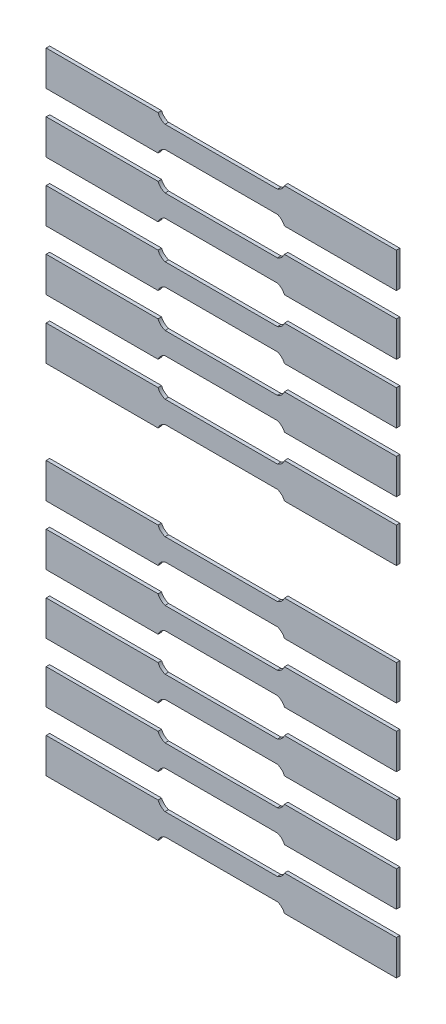
SolidWorks part; units mm, degrees
ref_plane "Ground Plane" through (0, 0, 0) normal (0, 0, 1) x (1, 0, 0)
ref_plane "Center Plane" through (0, 0, 0) normal (0, 1, 0) x (1, 0, 0)
ref_plane "Left Plane" through (0, 0, 0) normal (1, 0, 0) x (0, 0, -1)
ref_axis "FRONT (X)" through (88.99, 0, 0) along (-1, 0, 0)
ref_axis "LEFT (Y)" through (0, 55, 0) along (0, -1, 0)
ref_axis "UP (Z)" through (0, 0, 55) along (0, 0, -1)
sketch "Sketch1" plane through (0, 0, 0) normal (0, 0, 1) x (1, 0, 0)
  line L0 (0, 10) -> (0, 0)
  line L1 (66, 1.875) -> (66.044, 1.875)
  line L2 (66, 8.125) -> (66.044, 8.125)
  line L3 (34, 1.875) -> (33.956, 1.875)
  line L4 (0, 27) -> (0, 17)
  line L5 (66, 18.875) -> (66.044, 18.875)
  line L6 (66, 25.125) -> (66.044, 25.125)
  line L7 (34, 18.875) -> (33.956, 18.875)
  line L8 (0, 17) -> (31.956, 17)
  line L9 (0, 27) -> (31.956, 27)
  line L10 (100, 17) -> (100, 27)
  line L11 (49.956, 25.125) -> (66, 25.125)
  line L12 (66, 18.875) -> (50, 18.875)
  line L13 (50, 18.875) -> (34, 18.875)
  line L14 (33.956, 25.125) -> (49.956, 25.125)
  line L15 (68.044, 27) -> (100, 27)
  line L16 (68.044, 17) -> (100, 17)
  line L17 (0, 0) -> (31.956, 0)
  line L18 (0, 10) -> (31.956, 10)
  line L19 (100, 0) -> (100, 10)
  line L20 (49.956, 8.125) -> (66, 8.125)
  line L21 (66, 1.875) -> (50, 1.875)
  line L22 (50, 1.875) -> (34, 1.875)
  line L23 (33.956, 8.125) -> (49.956, 8.125)
  line L24 (68.044, 10) -> (100, 10)
  line L25 (68.044, 0) -> (100, 0)
  line L26 (33.956, 1.875) -> (31.956, 1.875) construction
  line L27 (31.956, 1.875) -> (31.956, 0) construction
  line L28 (33.956, 8.125) -> (31.956, 8.125) construction
  line L29 (31.956, 8.125) -> (31.956, 10) construction
  line L30 (68.044, 0) -> (68.044, 1.875) construction
  line L31 (68.044, 1.875) -> (66.044, 1.875) construction
  line L32 (66.044, 8.125) -> (68.044, 8.125) construction
  line L33 (68.044, 8.125) -> (68.044, 10) construction
  line L34 (33.956, 18.875) -> (31.956, 18.875) construction
  line L35 (31.956, 18.875) -> (31.956, 17) construction
  line L36 (33.956, 25.125) -> (31.956, 25.125) construction
  line L37 (31.956, 25.125) -> (31.956, 27) construction
  line L38 (68.044, 17) -> (68.044, 18.875) construction
  line L39 (68.044, 18.875) -> (66.044, 18.875) construction
  line L40 (66.044, 25.125) -> (68.044, 25.125) construction
  line L41 (68.044, 25.125) -> (68.044, 27) construction
  line L42 (0, 44) -> (0, 34)
  line L43 (66, 35.875) -> (66.044, 35.875)
  line L44 (66, 42.125) -> (66.044, 42.125)
  line L45 (34, 35.875) -> (33.956, 35.875)
  line L46 (0, 34) -> (31.956, 34)
  line L47 (0, 44) -> (31.956, 44)
  line L48 (100, 34) -> (100, 44)
  line L49 (49.956, 42.125) -> (66, 42.125)
  line L50 (66, 35.875) -> (50, 35.875)
  line L51 (50, 35.875) -> (34, 35.875)
  line L52 (33.956, 42.125) -> (49.956, 42.125)
  line L53 (68.044, 44) -> (100, 44)
  line L54 (68.044, 34) -> (100, 34)
  line L55 (33.956, 35.875) -> (31.956, 35.875) construction
  line L56 (31.956, 35.875) -> (31.956, 34) construction
  line L57 (33.956, 42.125) -> (31.956, 42.125) construction
  line L58 (31.956, 42.125) -> (31.956, 44) construction
  line L59 (68.044, 34) -> (68.044, 35.875) construction
  line L60 (68.044, 35.875) -> (66.044, 35.875) construction
  line L61 (66.044, 42.125) -> (68.044, 42.125) construction
  line L62 (68.044, 42.125) -> (68.044, 44) construction
  line L63 (0, 61) -> (0, 51)
  line L64 (66, 52.875) -> (66.044, 52.875)
  line L65 (66, 59.125) -> (66.044, 59.125)
  line L66 (34, 52.875) -> (33.956, 52.875)
  line L67 (0, 51) -> (31.956, 51)
  line L68 (0, 61) -> (31.956, 61)
  line L69 (100, 51) -> (100, 61)
  line L70 (49.956, 59.125) -> (66, 59.125)
  line L71 (66, 52.875) -> (50, 52.875)
  line L72 (50, 52.875) -> (34, 52.875)
  line L73 (33.956, 59.125) -> (49.956, 59.125)
  line L74 (68.044, 61) -> (100, 61)
  line L75 (68.044, 51) -> (100, 51)
  line L76 (33.956, 52.875) -> (31.956, 52.875) construction
  line L77 (31.956, 52.875) -> (31.956, 51) construction
  line L78 (33.956, 59.125) -> (31.956, 59.125) construction
  line L79 (31.956, 59.125) -> (31.956, 61) construction
  line L80 (68.044, 51) -> (68.044, 52.875) construction
  line L81 (68.044, 52.875) -> (66.044, 52.875) construction
  line L82 (66.044, 59.125) -> (68.044, 59.125) construction
  line L83 (68.044, 59.125) -> (68.044, 61) construction
  line L84 (0, 78) -> (0, 68)
  line L85 (66, 69.875) -> (66.044, 69.875)
  line L86 (66, 76.125) -> (66.044, 76.125)
  line L87 (34, 69.875) -> (33.956, 69.875)
  line L88 (0, 68) -> (31.956, 68)
  line L89 (0, 78) -> (31.956, 78)
  line L90 (100, 68) -> (100, 78)
  line L91 (49.956, 76.125) -> (66, 76.125)
  line L92 (66, 69.875) -> (50, 69.875)
  line L93 (50, 69.875) -> (34, 69.875)
  line L94 (33.956, 76.125) -> (49.956, 76.125)
  line L95 (68.044, 78) -> (100, 78)
  line L96 (68.044, 68) -> (100, 68)
  line L97 (33.956, 69.875) -> (31.956, 69.875) construction
  line L98 (31.956, 69.875) -> (31.956, 68) construction
  line L99 (33.956, 76.125) -> (31.956, 76.125) construction
  line L100 (31.956, 76.125) -> (31.956, 78) construction
  line L101 (68.044, 68) -> (68.044, 69.875) construction
  line L102 (68.044, 69.875) -> (66.044, 69.875) construction
  line L103 (66.044, 76.125) -> (68.044, 76.125) construction
  line L104 (68.044, 76.125) -> (68.044, 78) construction
  line L126 (0, 112) -> (0, 102)
  line L127 (66, 103.875) -> (66.044, 103.875)
  line L128 (66, 110.125) -> (66.044, 110.125)
  line L129 (34, 103.875) -> (33.956, 103.875)
  line L130 (0, 102) -> (31.956, 102)
  line L131 (0, 112) -> (31.956, 112)
  line L132 (100, 102) -> (100, 112)
  line L133 (49.956, 110.125) -> (66, 110.125)
  line L134 (66, 103.875) -> (50, 103.875)
  line L135 (50, 103.875) -> (34, 103.875)
  line L136 (33.956, 110.125) -> (49.956, 110.125)
  line L137 (68.044, 112) -> (100, 112)
  line L138 (68.044, 102) -> (100, 102)
  line L139 (33.956, 103.875) -> (31.956, 103.875) construction
  line L140 (31.956, 103.875) -> (31.956, 102) construction
  line L141 (33.956, 110.125) -> (31.956, 110.125) construction
  line L142 (31.956, 110.125) -> (31.956, 112) construction
  line L143 (68.044, 102) -> (68.044, 103.875) construction
  line L144 (68.044, 103.875) -> (66.044, 103.875) construction
  line L145 (66.044, 110.125) -> (68.044, 110.125) construction
  line L146 (68.044, 110.125) -> (68.044, 112) construction
  line L147 (0, 129) -> (0, 119)
  line L148 (66, 120.875) -> (66.044, 120.875)
  line L149 (66, 127.125) -> (66.044, 127.125)
  line L150 (34, 120.875) -> (33.956, 120.875)
  line L151 (0, 119) -> (31.956, 119)
  line L152 (0, 129) -> (31.956, 129)
  line L153 (100, 119) -> (100, 129)
  line L154 (49.956, 127.125) -> (66, 127.125)
  line L155 (66, 120.875) -> (50, 120.875)
  line L156 (50, 120.875) -> (34, 120.875)
  line L157 (33.956, 127.125) -> (49.956, 127.125)
  line L158 (68.044, 129) -> (100, 129)
  line L159 (68.044, 119) -> (100, 119)
  line L160 (33.956, 120.875) -> (31.956, 120.875) construction
  line L161 (31.956, 120.875) -> (31.956, 119) construction
  line L162 (33.956, 127.125) -> (31.956, 127.125) construction
  line L163 (31.956, 127.125) -> (31.956, 129) construction
  line L164 (68.044, 119) -> (68.044, 120.875) construction
  line L165 (68.044, 120.875) -> (66.044, 120.875) construction
  line L166 (66.044, 127.125) -> (68.044, 127.125) construction
  line L167 (68.044, 127.125) -> (68.044, 129) construction
  line L168 (0, 146) -> (0, 136)
  line L169 (66, 137.875) -> (66.044, 137.875)
  line L170 (66, 144.125) -> (66.044, 144.125)
  line L171 (34, 137.875) -> (33.956, 137.875)
  line L172 (0, 136) -> (31.956, 136)
  line L173 (0, 146) -> (31.956, 146)
  line L174 (100, 136) -> (100, 146)
  line L175 (49.956, 144.125) -> (66, 144.125)
  line L176 (66, 137.875) -> (50, 137.875)
  line L177 (50, 137.875) -> (34, 137.875)
  line L178 (33.956, 144.125) -> (49.956, 144.125)
  line L179 (68.044, 146) -> (100, 146)
  line L180 (68.044, 136) -> (100, 136)
  line L181 (33.956, 137.875) -> (31.956, 137.875) construction
  line L182 (31.956, 137.875) -> (31.956, 136) construction
  line L183 (33.956, 144.125) -> (31.956, 144.125) construction
  line L184 (31.956, 144.125) -> (31.956, 146) construction
  line L185 (68.044, 136) -> (68.044, 137.875) construction
  line L186 (68.044, 137.875) -> (66.044, 137.875) construction
  line L187 (66.044, 144.125) -> (68.044, 144.125) construction
  line L188 (68.044, 144.125) -> (68.044, 146) construction
  line L189 (0, 163) -> (0, 153)
  line L190 (66, 154.875) -> (66.044, 154.875)
  line L191 (66, 161.125) -> (66.044, 161.125)
  line L192 (34, 154.875) -> (33.956, 154.875)
  line L193 (0, 153) -> (31.956, 153)
  line L194 (0, 163) -> (31.956, 163)
  line L195 (100, 153) -> (100, 163)
  line L196 (49.956, 161.125) -> (66, 161.125)
  line L197 (66, 154.875) -> (50, 154.875)
  line L198 (50, 154.875) -> (34, 154.875)
  line L199 (33.956, 161.125) -> (49.956, 161.125)
  line L200 (68.044, 163) -> (100, 163)
  line L201 (68.044, 153) -> (100, 153)
  line L202 (33.956, 154.875) -> (31.956, 154.875) construction
  line L203 (31.956, 154.875) -> (31.956, 153) construction
  line L204 (33.956, 161.125) -> (31.956, 161.125) construction
  line L205 (31.956, 161.125) -> (31.956, 163) construction
  line L206 (68.044, 153) -> (68.044, 154.875) construction
  line L207 (68.044, 154.875) -> (66.044, 154.875) construction
  line L208 (66.044, 161.125) -> (68.044, 161.125) construction
  line L209 (68.044, 161.125) -> (68.044, 163) construction
  line L210 (0, 180) -> (0, 170)
  line L211 (66, 171.875) -> (66.044, 171.875)
  line L212 (66, 178.125) -> (66.044, 178.125)
  line L213 (34, 171.875) -> (33.956, 171.875)
  line L214 (0, 170) -> (31.956, 170)
  line L215 (0, 180) -> (31.956, 180)
  line L216 (100, 170) -> (100, 180)
  line L217 (49.956, 178.125) -> (66, 178.125)
  line L218 (66, 171.875) -> (50, 171.875)
  line L219 (50, 171.875) -> (34, 171.875)
  line L220 (33.956, 178.125) -> (49.956, 178.125)
  line L221 (68.044, 180) -> (100, 180)
  line L222 (68.044, 170) -> (100, 170)
  line L223 (33.956, 171.875) -> (31.956, 171.875) construction
  line L224 (31.956, 171.875) -> (31.956, 170) construction
  line L225 (33.956, 178.125) -> (31.956, 178.125) construction
  line L226 (31.956, 178.125) -> (31.956, 180) construction
  line L227 (68.044, 170) -> (68.044, 171.875) construction
  line L228 (68.044, 171.875) -> (66.044, 171.875) construction
  line L229 (66.044, 178.125) -> (68.044, 178.125) construction
  line L230 (68.044, 178.125) -> (68.044, 180) construction
  line L231 (0, 95) -> (0, 85) [skipped]
  line L232 (66, 86.875) -> (66.044, 86.875) [skipped]
  line L233 (66, 93.125) -> (66.044, 93.125) [skipped]
  line L234 (34, 86.875) -> (33.956, 86.875) [skipped]
  line L235 (0, 85) -> (31.956, 85) [skipped]
  line L236 (0, 95) -> (31.956, 95) [skipped]
  line L237 (100, 85) -> (100, 95) [skipped]
  line L238 (49.956, 93.125) -> (66, 93.125) [skipped]
  line L239 (66, 86.875) -> (50, 86.875) [skipped]
  line L240 (50, 86.875) -> (34, 86.875) [skipped]
  line L241 (33.956, 93.125) -> (49.956, 93.125) [skipped]
  line L242 (68.044, 95) -> (100, 95) [skipped]
  line L243 (68.044, 85) -> (100, 85) [skipped]
  line L244 (33.956, 86.875) -> (31.956, 86.875) construction
  line L245 (31.956, 86.875) -> (31.956, 85) construction
  line L246 (33.956, 93.125) -> (31.956, 93.125) construction
  line L247 (31.956, 93.125) -> (31.956, 95) construction
  line L248 (68.044, 85) -> (68.044, 86.875) construction
  line L249 (68.044, 86.875) -> (66.044, 86.875) construction
  line L250 (66.044, 93.125) -> (68.044, 93.125) construction
  line L251 (68.044, 93.125) -> (68.044, 95) construction
  arc A0 (33.956, 25.125) -> (31.956, 27) centre (34.9695, 28.2102) cw
  arc A1 (33.956, 18.875) -> (31.956, 17) centre (34.9695, 15.7898) ccw
  arc A2 (66.044, 18.875) -> (68.044, 17) centre (65.0305, 15.7898) cw
  arc A3 (66.044, 25.125) -> (68.044, 27) centre (65.0305, 28.2102) ccw
  arc A4 (33.956, 8.125) -> (31.956, 10) centre (34.9695, 11.2102) cw
  arc A5 (33.956, 1.875) -> (31.956, 0) centre (34.9695, -1.2102) ccw
  arc A6 (66.044, 1.875) -> (68.044, 0) centre (65.0305, -1.2102) cw
  arc A7 (66.044, 8.125) -> (68.044, 10) centre (65.0305, 11.2102) ccw
  arc A8 (33.956, 42.125) -> (31.956, 44) centre (34.9695, 45.2102) cw
  arc A9 (33.956, 35.875) -> (31.956, 34) centre (34.9695, 32.7898) ccw
  arc A10 (66.044, 35.875) -> (68.044, 34) centre (65.0305, 32.7898) cw
  arc A11 (66.044, 42.125) -> (68.044, 44) centre (65.0305, 45.2102) ccw
  arc A12 (33.956, 59.125) -> (31.956, 61) centre (34.9695, 62.2102) cw
  arc A13 (33.956, 52.875) -> (31.956, 51) centre (34.9695, 49.7898) ccw
  arc A14 (66.044, 52.875) -> (68.044, 51) centre (65.0305, 49.7898) cw
  arc A15 (66.044, 59.125) -> (68.044, 61) centre (65.0305, 62.2102) ccw
  arc A16 (33.956, 76.125) -> (31.956, 78) centre (34.9695, 79.2102) cw
  arc A17 (33.956, 69.875) -> (31.956, 68) centre (34.9695, 66.7898) ccw
  arc A18 (66.044, 69.875) -> (68.044, 68) centre (65.0305, 66.7898) cw
  arc A19 (66.044, 76.125) -> (68.044, 78) centre (65.0305, 79.2102) ccw
  arc A24 (33.956, 110.125) -> (31.956, 112) centre (34.9695, 113.2102) cw
  arc A25 (33.956, 103.875) -> (31.956, 102) centre (34.9695, 100.7898) ccw
  arc A26 (66.044, 103.875) -> (68.044, 102) centre (65.0305, 100.7898) cw
  arc A27 (66.044, 110.125) -> (68.044, 112) centre (65.0305, 113.2102) ccw
  arc A28 (33.956, 127.125) -> (31.956, 129) centre (34.9695, 130.2102) cw
  arc A29 (33.956, 120.875) -> (31.956, 119) centre (34.9695, 117.7898) ccw
  arc A30 (66.044, 120.875) -> (68.044, 119) centre (65.0305, 117.7898) cw
  arc A31 (66.044, 127.125) -> (68.044, 129) centre (65.0305, 130.2102) ccw
  arc A32 (33.956, 144.125) -> (31.956, 146) centre (34.9695, 147.2102) cw
  arc A33 (33.956, 137.875) -> (31.956, 136) centre (34.9695, 134.7898) ccw
  arc A34 (66.044, 137.875) -> (68.044, 136) centre (65.0305, 134.7898) cw
  arc A35 (66.044, 144.125) -> (68.044, 146) centre (65.0305, 147.2102) ccw
  arc A36 (33.956, 161.125) -> (31.956, 163) centre (34.9695, 164.2102) cw
  arc A37 (33.956, 154.875) -> (31.956, 153) centre (34.9695, 151.7898) ccw
  arc A38 (66.044, 154.875) -> (68.044, 153) centre (65.0305, 151.7898) cw
  arc A39 (66.044, 161.125) -> (68.044, 163) centre (65.0305, 164.2102) ccw
  arc A40 (33.956, 178.125) -> (31.956, 180) centre (34.9695, 181.2102) cw
  arc A41 (33.956, 171.875) -> (31.956, 170) centre (34.9695, 168.7898) ccw
  arc A42 (66.044, 171.875) -> (68.044, 170) centre (65.0305, 168.7898) cw
  arc A43 (66.044, 178.125) -> (68.044, 180) centre (65.0305, 181.2102) ccw
  arc A44 (33.956, 93.125) -> (31.956, 95) centre (34.9695, 96.2102) cw [skipped]
  arc A45 (33.956, 86.875) -> (31.956, 85) centre (34.9695, 83.7898) ccw [skipped]
  arc A46 (66.044, 86.875) -> (68.044, 85) centre (65.0305, 83.7898) cw [skipped]
  arc A47 (66.044, 93.125) -> (68.044, 95) centre (65.0305, 96.2102) ccw [skipped]
  dimension "D1" = 100
  dimension "D2" = 10
  dimension "D3" = 11
extrude "Boss-Extrude1" add sketch "Sketch1" against normal blind 1
